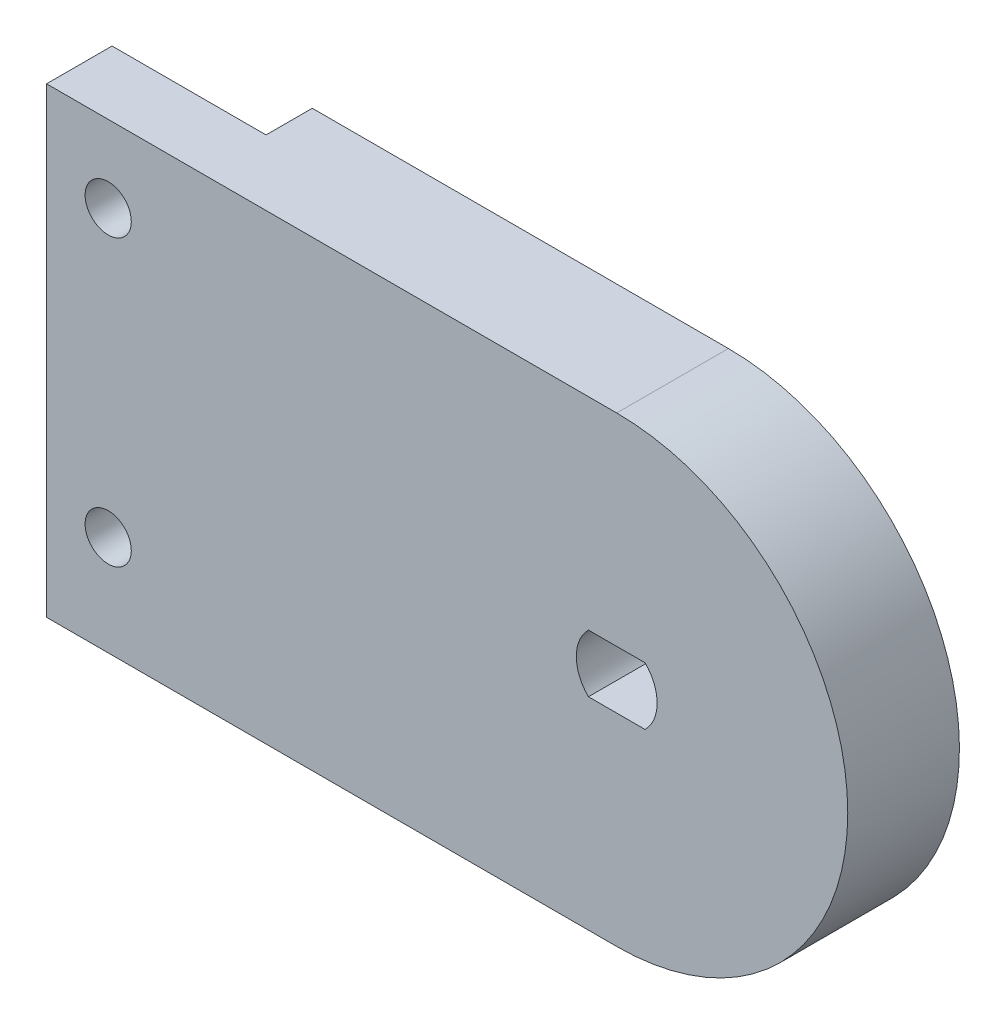
SolidWorks part; units mm, degrees
ref_plane "Front Plane" through (0, 0, 0) normal (0, 0, 1) x (1, 0, 0)
ref_plane "Top Plane" through (0, 0, 0) normal (0, 1, 0) x (1, 0, 0)
ref_plane "Right Plane" through (0, 0, 0) normal (1, 0, 0) x (0, 0, -1)
sketch "Sketch2" plane through (0, 0, -8) normal (0, 0, 1) x (1, 0, 0)
  line L0 (-25.7692, 245.1803) -> (-54.7874, 245.1803)
  line L1 (-54.7874, 245.1803) -> (-54.7874, 215.1803)
  line L2 (-54.7874, 215.1803) -> (-25.7692, 215.1803)
  arc A2 (-25.7692, 215.1803) -> (-25.7692, 245.1803) centre (-25.7692, 230.1803) ccw
  dimension "D1" = 29.0182
extrude "Boss-Extrude1" add sketch "Sketch2" along normal blind 8
sketch "Sketch3" plane through (0, 0, -28) normal (0, 0, -1) x (-1, 0, 0)
  line L3 (25.7692, 215.1803) -> (54.7874, 215.1803)
  line L4 (54.7874, 215.1803) -> (54.7874, 245.1803)
  line L5 (54.7874, 245.1803) -> (25.7692, 245.1803)
  line L6 (25.7692, 215.1803) -> (54.7874, 215.1803)
  line L7 (54.7874, 215.1803) -> (54.7874, 245.1803)
  line L8 (54.7874, 245.1803) -> (25.7692, 245.1803)
  arc A1 (25.7692, 245.1803) -> (25.7692, 215.1803) centre (25.7692, 230.1803) ccw
  arc A2 (25.7692, 245.1803) -> (25.7692, 215.1803) centre (25.7692, 230.1803) ccw
  dimension "D1" = 0
extrude "Boss-Extrude2" add sketch "Sketch3" along normal blind 8 separate body
sketch "Sketch4" plane through (-54.7874, 0, 0) normal (-1, 0, 0) x (0, 0, 1)
  line L1 (-36, 245.1803) -> (0, 245.1803)
  line L2 (-36, 245.1803) -> (-36, 215.1803)
  line L3 (-36, 215.1803) -> (0, 215.1803)
  line L4 (0, 245.1803) -> (0, 215.1803)
extrude "Boss-Extrude3" add sketch "Sketch4" along normal blind 8
sketch "Sketch5" plane through (-62.7874, 0, 0) normal (-1, 0, 0) x (0, 0, 1)
  circle A1 centre (-18, 230.1803) radius 7
  circle A2 centre (-18, 230.1803) radius 5
extrude "Boss-Extrude4" add sketch "Sketch5" along normal blind 10
chamfer "Chamfer1" distance 3 angle 45 1 edges at (-62.7874, 230.1803, -11)
sketch "Sketch6" plane through (0, 0, -36) normal (0, 0, -1) x (-1, 0, 0)
  line L0 (23.9321, 232.0553) -> (27.6063, 232.0553)
  line L1 (23.9321, 228.3053) -> (27.6063, 228.3053)
  arc A0 (23.9321, 232.0553) -> (23.9321, 228.3053) centre (25.7692, 230.1803) ccw
  arc A1 (27.6063, 228.3053) -> (27.6063, 232.0553) centre (25.7692, 230.1803) ccw
  dimension "D1" = 1.875
  dimension "D2" = 3.75
extrude "Cut-Extrude1" cut sketch "Sketch6" against normal up to surface (36 mm away) up to face at (-40.5283, 230.1803, 0)
sketch "Sketch7" plane through (-62.7874, 0, 0) normal (-1, 0, 0) x (0, 0, 1)
  line L0 (0, 215.1803) -> (0, 218.1803)
  line L1 (0, 215.1803) -> (0, 245.1803) construction
  line L2 (0, 215.1803) -> (-3, 215.1803)
  line L3 (-36, 215.1803) -> (0, 215.1803) construction
  line L4 (-18, 215.1803) -> (-18, 245.1803) construction
  line L5 (0, 245.1803) -> (-36, 245.1803) construction
  line L6 (-36, 215.1803) -> (-33, 215.1803)
  line L7 (-36, 215.1803) -> (-36, 218.1803)
  arc A0 (0, 218.1803) -> (-3, 215.1803) centre (-3, 218.1803) cw
  arc A1 (-36, 218.1803) -> (-33, 215.1803) centre (-33, 218.1803) ccw
extrude "Cut-Extrude2" cut sketch "Sketch7" against normal through all
sketch "Sketch8" plane through (0, 215.1803, 0) normal (0, -1, 0) x (1, 0, 0)
  line L0 (-54.7874, -8) -> (-25.7692, -8) construction
  line L1 (-56.7874, -28) -> (-39.7874, -28)
  line L2 (-56.7874, -28) -> (-56.7874, -8)
  line L3 (-56.7874, -8) -> (-39.7874, -8)
  line L4 (-39.7874, -28) -> (-39.7874, -8)
extrude "Boss-Extrude5" add sketch "Sketch8" against normal blind 7
sketch "Sketch10" plane through (0, 0, -28) normal (0, 0, 1) x (1, 0, 0)
  line L5 (-54.7874, 222.1803) -> (-39.7874, 222.1803)
  line L6 (-39.7874, 222.1803) -> (-39.7874, 215.1803)
  line L7 (-39.7874, 215.1803) -> (-25.7692, 215.1803)
  line L8 (-25.7692, 245.1803) -> (-54.7874, 245.1803)
  line L9 (-54.7874, 245.1803) -> (-54.7874, 222.1803)
  line L10 (-54.7874, 222.1803) -> (-39.7874, 222.1803)
  line L11 (-39.7874, 222.1803) -> (-39.7874, 215.1803)
  line L12 (-39.7874, 215.1803) -> (-25.7692, 215.1803)
  line L13 (-25.7692, 245.1803) -> (-54.7874, 245.1803)
  line L14 (-54.7874, 245.1803) -> (-54.7874, 222.1803)
  arc A1 (-25.7692, 215.1803) -> (-25.7692, 245.1803) centre (-25.7692, 230.1803) ccw
  arc A2 (-25.7692, 215.1803) -> (-25.7692, 245.1803) centre (-25.7692, 230.1803) ccw
  dimension "D1" = 0
extrude "Cut-Extrude3" cut sketch "Sketch10" against normal blind 0.75
sketch "Sketch11" plane through (0, 0, -8) normal (0, 0, -1) x (-1, 0, 0)
  line L5 (25.7692, 215.1803) -> (39.7874, 215.1803)
  line L6 (39.7874, 215.1803) -> (39.7874, 222.1803)
  line L7 (39.7874, 222.1803) -> (54.7874, 222.1803)
  line L8 (54.7874, 222.1803) -> (54.7874, 245.1803)
  line L9 (54.7874, 245.1803) -> (25.7692, 245.1803)
  line L10 (25.7692, 215.1803) -> (39.7874, 215.1803)
  line L11 (39.7874, 215.1803) -> (39.7874, 222.1803)
  line L12 (39.7874, 222.1803) -> (54.7874, 222.1803)
  line L13 (54.7874, 222.1803) -> (54.7874, 245.1803)
  line L14 (54.7874, 245.1803) -> (25.7692, 245.1803)
  arc A1 (25.7692, 245.1803) -> (25.7692, 215.1803) centre (25.7692, 230.1803) ccw
  arc A2 (25.7692, 245.1803) -> (25.7692, 215.1803) centre (25.7692, 230.1803) ccw
  dimension "D1" = 0
extrude "Cut-Extrude4" cut sketch "Sketch11" against normal blind 0.75
sketch "Sketch12" plane through (-62.7874, 0, 0) normal (-1, 0, 0) x (0, 0, 1)
  line L1 (-23.75, 242.6803) -> (-12.25, 242.6803)
  line L2 (-24.75, 241.6803) -> (-24.75, 239.1803)
  line L3 (-23.75, 238.1803) -> (-12.25, 238.1803)
  line L4 (-7.25, 245.1803) -> (-28.75, 245.1803)
  line L5 (-7.25, 222.1803) -> (-7.25, 245.1803)
  line L6 (-28.75, 222.1803) -> (-7.25, 222.1803)
  line L7 (-28.75, 245.1803) -> (-28.75, 222.1803)
  line L8 (-7.25, 245.1803) -> (-28.75, 245.1803) construction
  line L9 (-7.25, 222.1803) -> (-7.25, 245.1803) construction
  line L10 (-28.75, 222.1803) -> (-7.25, 222.1803) construction
  line L11 (-28.75, 245.1803) -> (-28.75, 222.1803) construction
  line L12 (-11.25, 241.6803) -> (-11.25, 239.1803)
  arc A0 (-12.25, 238.1803) -> (-11.25, 239.1803) centre (-12.25, 239.1803) ccw
  arc A1 (-12.25, 242.6803) -> (-11.25, 241.6803) centre (-12.25, 241.6803) cw
  arc A2 (-23.75, 242.6803) -> (-24.75, 241.6803) centre (-23.75, 241.6803) ccw
  arc A3 (-24.75, 239.1803) -> (-23.75, 238.1803) centre (-23.75, 239.1803) ccw
  point P10 (-11.25, 238.1803)
  point P13 (-11.25, 242.6803)
  dimension "D6" = 1
  dimension "D1" = 0
extrude "Cut-Extrude5" cut sketch "Sketch12" against normal through all both and the other way through all
sketch "Sketch13" plane through (0, 0, -36) normal (0, 0, -1) x (-1, 0, 0)
  line L1 (52.7874, 245.1803) -> (65.2203, 245.1803)
  line L2 (52.7874, 245.1803) -> (52.7874, 215.1803)
  line L3 (52.7874, 215.1803) -> (65.2203, 215.1803)
  line L4 (65.2203, 245.1803) -> (65.2203, 215.1803)
extrude "Cut-Extrude6" cut sketch "Sketch13" against normal blind 3
sketch "Sketch14" plane through (0, 0, 0) normal (0, 0, 1) x (1, 0, 0)
  line L4 (-52.7874, 245.1803) -> (-62.7874, 245.1803)
  line L5 (-52.7874, 215.1803) -> (-52.7874, 245.1803)
  line L6 (-62.7874, 215.1803) -> (-52.7874, 215.1803)
  line L7 (-62.7874, 245.1803) -> (-62.7874, 215.1803)
  line L8 (-52.7874, 245.1803) -> (-62.7874, 245.1803)
  line L9 (-52.7874, 215.1803) -> (-52.7874, 245.1803)
  line L10 (-62.7874, 215.1803) -> (-52.7874, 215.1803)
  line L11 (-62.7874, 245.1803) -> (-62.7874, 215.1803)
  dimension "D1" = 0
extrude "Cut-Extrude7" cut sketch "Sketch14" against normal blind 3
sketch "Sketch15" plane through (0, 0, 0) normal (0, 0, 1) x (1, 0, 0)
  spline S0 degree 3 poles (-58.7873, 241.6803) (-61.7873, 241.6803) (-61.7873, 238.6803) (-58.7873, 238.6803) (-55.7873, 238.6803) (-55.7873, 241.6803) (-58.7873, 241.6803) (-61.7873, 241.6803) (-61.7873, 238.6803) knots -0.5 0 0 0 0.5 0.5 0.5 1 1 1 1.5 1.5 1.5 weights 1 0.333333 0.333333 1 0.333333 0.333333 1 0.333333 0.333333 only from (-58.7873, 241.6803) to (-58.7873, 241.6803) construction
  spline S1 degree 3 poles (-58.7873, 223.18) (-61.7873, 223.18) (-61.7873, 220.18) (-58.7873, 220.18) (-55.7873, 220.18) (-55.7873, 223.18) (-58.7873, 223.18) (-61.7873, 223.18) (-61.7873, 220.18) knots -0.5 0 0 0 0.5 0.5 0.5 1 1 1 1.5 1.5 1.5 weights 1 0.333333 0.333333 1 0.333333 0.333333 1 0.333333 0.333333 only from (-58.7873, 223.18) to (-58.7873, 223.18) construction
  spline S2 degree 3 poles (-58.7873, 241.6803) (-61.7873, 241.6803) (-61.7873, 238.6803) (-58.7873, 238.6803) (-55.7873, 238.6803) (-55.7873, 241.6803) (-58.7873, 241.6803) (-61.7873, 241.6803) (-61.7873, 238.6803) knots -0.5 0 0 0 0.5 0.5 0.5 1 1 1 1.5 1.5 1.5 weights 1 0.333333 0.333333 1 0.333333 0.333333 1 0.333333 0.333333 only from (-58.7873, 241.6803) to (-58.7873, 241.6803)
  spline S3 degree 3 poles (-58.7873, 223.18) (-61.7873, 223.18) (-61.7873, 220.18) (-58.7873, 220.18) (-55.7873, 220.18) (-55.7873, 223.18) (-58.7873, 223.18) (-61.7873, 223.18) (-61.7873, 220.18) knots -0.5 0 0 0 0.5 0.5 0.5 1 1 1 1.5 1.5 1.5 weights 1 0.333333 0.333333 1 0.333333 0.333333 1 0.333333 0.333333 only from (-58.7873, 223.18) to (-58.7873, 223.18)
extrude "Cut-Extrude8" cut sketch "Sketch15" against normal up to surface (36 mm away) up to face at (-25.7692, 230.1803, -36)
sketch "Sketch16" plane through (0, 0, 0) normal (0, 0, 1) x (1, 0, 0)
  line L1 (-8.857, 211.1546) -> (-76.0917, 211.1546)
  line L2 (-8.857, 211.1546) -> (-8.857, 248.0517)
  line L3 (-8.857, 248.0517) -> (-76.0917, 248.0517)
  line L4 (-76.0917, 211.1546) -> (-76.0917, 248.0517)
extrude "Cut-Extrude9" cut sketch "Sketch16" against normal up to surface (28.75 mm away) up to face at (-37.6147, 227.5136, -28.75)
